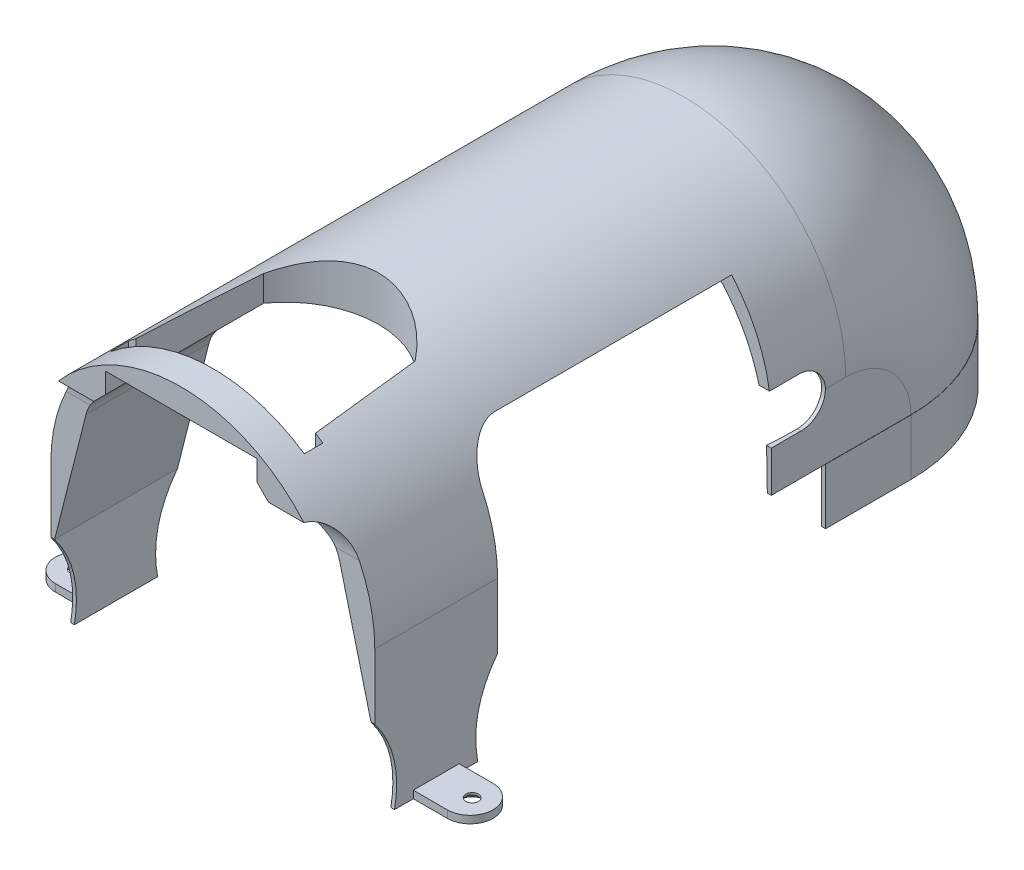
SolidWorks part; units mm, degrees
material "PET"
ref_plane "Front Plane" through (0, 0, 0) normal (0, 0, 1) x (1, 0, 0)
ref_plane "Top Plane" through (0, 0, 0) normal (0, 1, 0) x (1, 0, 0)
ref_plane "Right Plane" through (0, 0, 0) normal (1, 0, 0) x (0, 0, -1)
sketch "Sketch1" plane through (0, 0, 0) normal (0, 0, 1) x (1, 0, 0)
  line L0 (0, 0) -> (0, -87) construction
  line L1 (43.5, 0) -> (43.5, -87)
  line L2 (-43.5, 0) -> (-43.5, -87)
  arc A0 (43.5, 0) -> (-43.5, 0) centre (0, 0) ccw
  arc A1 (-43.5, -87) -> (43.5, -87) centre (0, -87) ccw
  point P3 (0, -43.5)
  dimension "D1" = 87
  dimension "D2" = 87
  dimension "D3" = 43.5
extrude "Boss-Extrude1" add sketch "Sketch1" along normal blind 135
sketch "Sketch2" plane through (43.5, 0, 0) normal (1, 0, 0) x (0, 0, -1)
  line L0 (0, -87) -> (0, 0) construction
  line L1 (-83.5, 28.5) -> (-20, 28.5)
  line L3 (-93.5, -41.5) -> (-20, -41.5)
  line L4 (-20, 28.5) -> (-20, -41.5)
  line L5 (-93.5, 28.5) -> (-20, -41.5) construction
  line L6 (-93.5, -41.5) -> (-20, 28.5) construction
  line L7 (-93.5, 18.5) -> (-93.5, -17.5)
  line L8 (-93.5, -41.5) -> (-98.5, -41.5)
  line L9 (0, 43.5) -> (-135, 43.5) construction
  arc A0 (-83.5, 28.5) -> (-93.5, 18.5) centre (-83.5, 18.5) ccw
  spline S0 degree 2 poles (-93.5, -17.5) (-101.6199, -28.176) (-98.5, -41.5) knots 0 0 0 1 1 1
  point P0 (-56.75, -6.5)
  dimension "D3" = 10
  dimension "D1" = 20
  dimension "D2" = 15
extrude "Cut-Extrude1" cut sketch "Sketch2" against normal blind 135
ref_plane "Plane1" through (0, 0, 110) normal (0, 0, 1) x (1, 0, 0)
mirror "Mirror1" about plane through (0, 0, 110) normal (0, 0, 1) of "Cut-Extrude1"
sketch "Sketch4" plane through (43.5, 0, 0) normal (1, 0, 0) x (0, 0, -1)
  line L0 (-20.0357, 0) -> (-11.96, 0) construction
  line L1 (-20.0357, 6.5) -> (-11.96, 6.5)
  line L2 (-20.0357, -6.5) -> (-11.96, -6.5)
  arc A0 (-20.0357, 6.5) -> (-20.0357, -6.5) centre (-20.0357, 0) ccw
  arc A1 (-11.96, -6.5) -> (-11.96, 6.5) centre (-11.96, 0) ccw
  point P2 (-15.9978, 0)
  dimension "D1" = 13
extrude "Cut-Extrude2" cut sketch "Sketch4" against normal blind 121
sketch "Sketch7" plane through (0, 0, 0) normal (0, 0, 1) x (1, 0, 0)
  line L0 (-43.5, 0) -> (-43.5, -17.5)
  line L1 (-43.5, -17.5) -> (-43.5, -41.5) construction
  line L2 (-43.5, -17.5) -> (43.5, -17.5) construction
  line L3 (-43.5, -17.5) -> (43.5, -17.5)
  line L4 (43.5, -17.5) -> (43.5, 0)
  arc A2 (43.5, 0) -> (-43.5, 0) centre (0, 0) ccw
  arc A3 (-39.37, 18.5) -> (-43.5, 0) centre (0, 0) ccw construction
revolve "Revolve1" add sketch "Sketch7" angle 90 about L3 reverse direction yes
ref_plane "Plane5" through (0, -40, 0) normal (0, 1, 0) x (1, 0, 0)
sketch "Sketch8" plane through (0, -40, 0) normal (0, 1, 0) x (1, 0, 0)
  line L1 (-50.7939, 59.5446) -> (50.7939, 59.5446)
  line L2 (-50.7939, 59.5446) -> (-50.7939, -142.4071)
  line L3 (-50.7939, -142.4071) -> (50.7939, -142.4071)
  line L4 (50.7939, 59.5446) -> (50.7939, -142.4071)
  line L5 (-50.7939, 59.5446) -> (50.7939, -142.4071) construction
  line L6 (-50.7939, -142.4071) -> (50.7939, 59.5446) construction
  point P0 (0, -41.4313)
extrude "Cut-Extrude3" cut sketch "Sketch8" against normal blind 135
sketch "Sketch9" plane through (0, 0, 110) normal (0, 0, 1) x (1, 0, 0)
  line L0 (-42.5, -40) -> (-42.5, -17.5)
  line L1 (43.5, -40) -> (-43.5, -40) construction
  line L2 (-43.5, -17.5) -> (43.5, -17.5) construction
  line L3 (-42.5, -17.5) -> (-34.0465, 15.8329)
  line L4 (-39.37, 18.5) -> (39.37, 18.5) construction
  line L5 (-31.4244, 20.4457) -> (-20.3455, 31.5246)
  line L6 (-20.3455, 31.5246) -> (20.3455, 31.5246)
  line L7 (20.3455, 31.5246) -> (31.4244, 20.4457)
  line L8 (34.0465, 15.8329) -> (42.5, -17.5)
  line L9 (42.5, -17.5) -> (42.5, -40)
  line L10 (42.5, -40) -> (-42.5, -40)
  line L11 (-43.5, -17.5) -> (-43.5, -40) construction
  line L12 (43.5, -40) -> (43.5, -17.5) construction
  arc A0 (-34.0465, 15.8329) -> (-31.4244, 20.4457) centre (-24.3533, 13.3746) cw
  arc A1 (31.4244, 20.4457) -> (34.0465, 15.8329) centre (24.3533, 13.3746) cw
  point P17 (-33.37, 18.5)
  point P20 (33.37, 18.5)
  dimension "D1" = 10
  dimension "D2" = 10
  dimension "D3" = 1
  dimension "D4" = 1
  dimension "D5" = 6
  dimension "D6" = 6
  dimension "D7" = 13
  dimension "D8" = 13
extrude "Cut-Extrude4" cut sketch "Sketch9" against normal blind 105 and the other way blind 64
ref_plane "Plane6" through (0, 0, 0) normal (0, 0, 1) x (1, 0, 0)
sketch "Sketch12" plane through (0, 0, 0) normal (0, 0, 1) x (1, 0, 0)
  line L0 (-43.5, -17.5) -> (-43.5, 0)
  line L1 (43.5, 0) -> (43.5, -17.5)
  line L2 (43.5, -17.5) -> (-43.5, -17.5)
  line L3 (-42.5, -17.5) -> (-42.5, 0)
  line L4 (42.5, 0) -> (42.5, -17.5)
  line L5 (42.5, -17.5) -> (-42.5, -17.5)
  arc A0 (-43.5, 0) -> (43.5, 0) centre (0, 0) cw
  arc A1 (43.5, 0) -> (-43.5, 0) centre (0, 0) ccw construction
  arc A2 (-42.5, 0) -> (42.5, 0) centre (0, 0) cw
revolve "Cut-Revolve3" cut sketch "Sketch12" angle 360 about L5 region at (0, 8.824, 0)
sketch "Sketch13" plane through (0, 0, 0) normal (0, 1, 0) x (1, 0, 0)
  line L0 (-27.6553, -126.4609) -> (24.5281, -126.4609)
  line L1 (24.5281, -121.4609) -> (22.5281, -121.4609)
  line L2 (22.5281, -121.4609) -> (20.37, -92.5312)
  line L3 (24.5281, -126.4609) -> (24.5281, -121.4609)
  line L4 (-27.6553, -126.4609) -> (-27.6553, -121.4609)
  line L5 (-27.6553, -121.4609) -> (-25.6553, -121.4609)
  line L6 (-25.6553, -121.4609) -> (-20.37, -92.5312)
  arc A0 (20.37, -92.5312) -> (-20.37, -92.5312) centre (0, -106.9063) ccw
  dimension "D1" = 2
  dimension "D2" = 2
  dimension "D3" = 5
  dimension "D4" = 5
  dimension "D5" = 19
  dimension "D6" = 19
extrude "Cut-Extrude6" cut sketch "Sketch13" along normal blind 88
ref_plane "Plane7" through (0, -40, 0) normal (0, 1, 0) x (1, 0, 0)
sketch "Sketch14" plane through (0, -40, 0) normal (0, 1, 0) x (1, 0, 0)
  line L0 (-43.5, -103.8527) -> (-52.6298, -103.8527)
  line L1 (-43.5, -126.5) -> (-43.5, -93.5) construction
  line L2 (-47.85, -110) -> (47.85, -110) construction
  line L3 (-52.6298, -116.1473) -> (-43.5, -116.1473)
  line L4 (-43.5, -103.8527) -> (-43.5, -116.1473)
  arc A0 (-52.6298, -103.8527) -> (-52.6298, -116.1473) centre (-52.6298, -110) ccw
extrude "Boss-Extrude2" add sketch "Sketch14" along normal blind 2
hole_wizard "CSK for M3 Countersunk Flat Head Screw1" positions "3DSketch2" profile "Sketch18" countersink size "M3" standard "ISO" end condition through all
sketch3d "3DSketch2"
  point P0 (-53.1592, -40, 109.996)
sketch "Sketch18" plane through (-53.1592, -40, 109.996) normal (1, 0, 0) x (0, 0, -1)
  line L0 (0, 0) -> (0, 83.5)
  line L1 (0, 83.5) -> (1.7, 83.5)
  line L2 (1.7, 83.5) -> (1.7, 1.45)
  line L3 (1.7, 1.45) -> (3.15, 0)
  line L5 (3.15, 0) -> (0, 0)
  line L6 (-1.7, 1.45) -> (-3.15, 0) construction
  line L11 (0, -6.35) -> (0, 107.95) construction
  dimension "Thru Hole Dia." = 3.4
  dimension "Thru Hole Depth" = 83.5
  dimension "Near C'Sink Dia." = 6.3
  dimension "Near C'Sink Angle" = 90
sketch "Sketch19" plane through (0, -40, 0) normal (0, 1, 0) x (1, 0, 0)
  line L6 (20.3455, -135) -> (20.3455, -126.4609) construction
  line L11 (-20.3455, -135) -> (20.3455, -135)
  line L12 (-20.3455, -135) -> (-20.3455, -127.4609)
  line L13 (-20.3455, -127.4609) -> (20.3455, -127.4609)
  line L14 (20.3455, -135) -> (20.3455, -127.4609)
  line L15 (-20.3455, -126.4609) -> (20.3455, -126.4609) construction
  dimension "D1" = 1
extrude "Cut-Extrude7" cut sketch "Sketch19" along normal blind 77
ref_plane "Plane11" through (0, -15, 0) normal (0, 1, 0) x (1, 0, 0)
mirror "Mirror2" about plane through (0, 0, 0) normal (1, 0, 0) of "CSK for M3 Countersunk Flat Head Screw1", "Boss-Extrude2"
ref_plane "Plane12" through (0, -17.5, 0) normal (0, -1, 0) x (-1, 0, 0)
sketch "Sketch28" plane through (0, -17.5, 0) normal (0, -1, 0) x (-1, 0, 0)
  line L1 (-47.167, 53.1294) -> (47.167, 53.1294)
  line L2 (-47.167, 53.1294) -> (-47.167, -53.1294)
  line L3 (-47.167, -53.1294) -> (47.167, -53.1294)
  line L4 (47.167, 53.1294) -> (47.167, -53.1294)
  line L5 (-47.167, 53.1294) -> (47.167, -53.1294) construction
  line L6 (-47.167, -53.1294) -> (47.167, 53.1294) construction
  point P0 (0, 0)
extrude "Cut-Extrude10" cut sketch "Sketch28" along normal blind 79
sketch "Sketch29" plane through (0, -17.5, 0) normal (0, -1, 0) x (-1, 0, 0)
  line L0 (0, 17.5) -> (0, -28.4788) construction
  line L1 (-70.137, -28.925) -> (55.3436, -28.1266) construction
  line L2 (42.4729, 17.5) -> (42.4729, -5.46)
  line L3 (-42.4729, 17.5) -> (-42.4729, -5.46)
  line L4 (0, 17.5) -> (0, -28.4788) construction
  line L6 (-43.5567, 17.5) -> (-43.5567, -5.4911)
  line L7 (-43.5, -5.46) -> (-42.4729, -5.46)
  line L8 (-43.5, -5.46) -> (-43.5567, -5.4911)
  line L9 (42.4729, -5.46) -> (43.5, -5.46)
  line L10 (43.5567, 17.5) -> (43.5, -5.46)
  arc A0 (42.4729, 17.5) -> (-42.4729, 17.5) centre (0, 17.5) ccw
  arc A2 (43.5567, 17.5) -> (-43.5567, 17.5) centre (0, 17.5) ccw
  point P5 (0, -5.4911)
  point P12 (0, -5.4911)
extrude "Boss-Extrude3" add sketch "Sketch29" along normal blind 15
